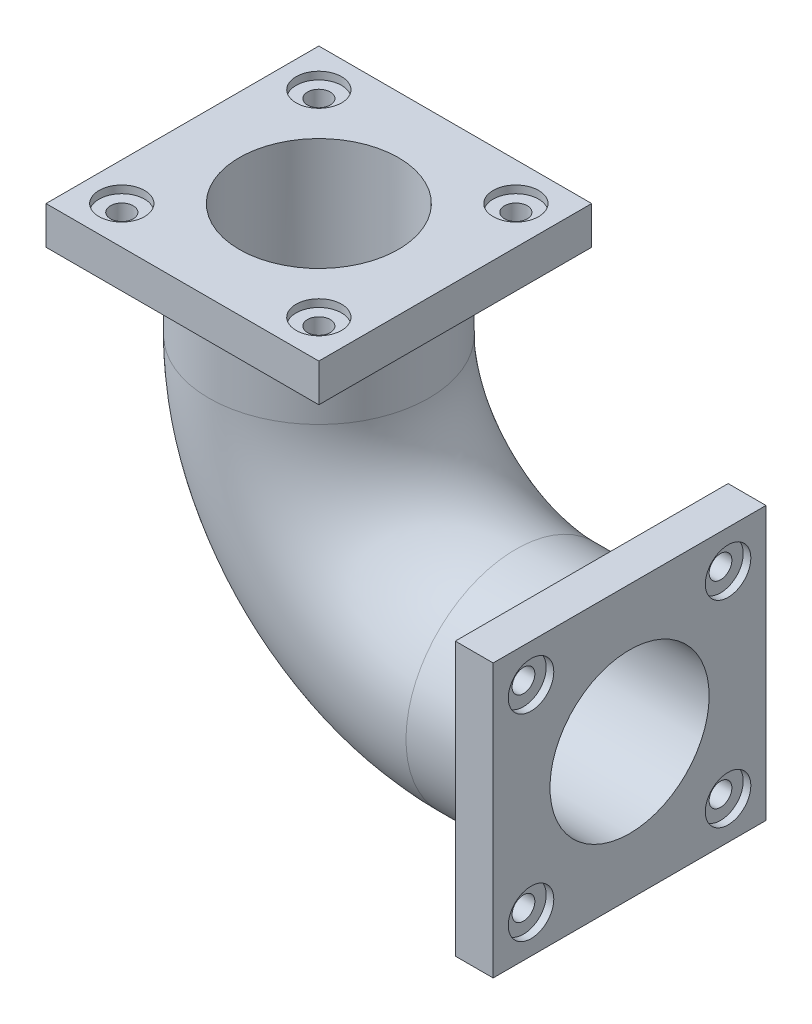
SolidWorks part; units mm, degrees
ref_plane "Ön Düzlem" through (0, 0, 0) normal (0, 0, 1) x (1, 0, 0)
ref_plane "Üst Düzlem" through (0, 0, 0) normal (0, 1, 0) x (1, 0, 0)
ref_plane "Sağ Düzlem" through (0, 0, 0) normal (1, 0, 0) x (0, 0, -1)
sketch "Çizim1" plane through (0, 0, 0) normal (0, 0, 1) x (1, 0, 0)
  line L0 (0, 0) -> (-150, 0)
  line L1 (-410, 260) -> (-410, 410)
  arc A0 (-150, 0) -> (-410, 260) centre (-150, 260) cw
  dimension "D3" = 260
  dimension "D1" = 150
  dimension "D2" = 150
  dimension "D4" = 410
sketch "Çizim4" plane through (0, 0, 0) normal (1, 0, 0) x (0, 0, -1)
  circle A0 centre (0, 0) radius 145
  dimension "D1" = 290
sweep "Süpür1" add profiles "Çizim4" path "Çizim1"
sketch "Çizim5" plane through (0, 410, 0) normal (0, 1, 0) x (1, 0, 0)
  line L0 (-410, 145) -> (-410, -145) construction
  line L3 (-590, 180) -> (-230, 180)
  line L4 (-590, 180) -> (-590, -180)
  line L5 (-590, -180) -> (-230, -180)
  line L6 (-230, 180) -> (-230, -180)
  line L7 (-590, 180) -> (-230, -180) construction
  line L8 (-590, -180) -> (-230, 180) construction
  point P2 (-410, 0)
  point P12 (-410, 0)
  dimension "D2" = 360
  dimension "D1" = 360
extrude "Yükseklik-Ekstrüzyon1" add sketch "Çizim5" against normal blind 50
sketch "Çizim6" plane through (0, 0, 0) normal (1, 0, 0) x (0, 0, -1)
  line L1 (-180, 180) -> (180, 180)
  line L2 (-180, 180) -> (-180, -180)
  line L3 (-180, -180) -> (180, -180)
  line L4 (180, 180) -> (180, -180)
  line L5 (-180, 180) -> (180, -180) construction
  line L6 (-180, -180) -> (180, 180) construction
  point P0 (0, 0)
  dimension "D1" = 360
  dimension "D2" = 360
extrude "Yükseklik-Ekstrüzyon2" add sketch "Çizim6" against normal blind 50
sketch "Çizim7" plane through (0, 410, 0) normal (0, 1, 0) x (1, 0, 0)
  line L0 (-230, 180) -> (-590, 180) construction
  line L1 (-590, 180) -> (-590, -180) construction
  line L2 (-590, -180) -> (-230, -180) construction
  line L3 (-230, -180) -> (-230, 180) construction
  circle A0 centre (-540, 130) radius 15
  circle A1 centre (-280, 130) radius 15
  circle A2 centre (-540, -130) radius 15
  circle A3 centre (-280, -130) radius 15
  point P12 (-802.0645, 261.2808)
  point P17 (0, 0)
  dimension "D3" = 30
  dimension "D5" = 30
  dimension "D7" = 30
  dimension "D1" = 50
  dimension "D2" = 50
  dimension "D4" = 50
  dimension "D6" = 50
extrude "Kes-Ekstrüzyon1" cut sketch "Çizim7" against normal blind 50
sketch "Çizim8" plane through (0, 410, 0) normal (0, 1, 0) x (1, 0, 0)
  circle A0 centre (-540, 130) radius 30
  circle A1 centre (-280, 130) radius 30
  circle A2 centre (-280, -130) radius 30
  circle A3 centre (-540, -130) radius 30
  dimension "D1" = 60
  dimension "D2" = 60
  dimension "D3" = 60
  dimension "D4" = 60
extrude "Kes-Ekstrüzyon2" cut sketch "Çizim8" against normal blind 10
sketch "Çizim9" plane through (0, 0, 0) normal (1, 0, 0) x (0, 0, -1)
  line L0 (-180, 180) -> (-180, -180) construction
  line L1 (180, 180) -> (-180, 180) construction
  line L2 (-180, -180) -> (180, -180) construction
  line L3 (180, -180) -> (180, 180) construction
  circle A0 centre (-130, 130) radius 15
  circle A1 centre (130, 130) radius 15
  circle A2 centre (130, -130) radius 15
  circle A3 centre (-130, -130) radius 15
  point P8 (114.6915, 128.9846)
  point P9 (-88.9783, 129.5306)
  point P10 (117.4216, -114.5455)
  dimension "D3" = 30
  dimension "D1" = 50
  dimension "D2" = 50
  dimension "D4" = 50
  dimension "D5" = 50
extrude "Yükseklik-Ekstrüzyon3" add sketch "Çizim9" against normal blind 50
extrude "Kes-Ekstrüzyon3" cut sketch "Çizim9<2>" against normal blind 50
sketch "Çizim9<2>" plane through (0, 0, 0) normal (1, 0, 0) x (0, 0, -1) same geometry as "Çizim9"
sketch "Çizim10" plane through (0, 0, 0) normal (1, 0, 0) x (0, 0, -1)
  circle A0 centre (-130, 130) radius 30
  circle A1 centre (130, 130) radius 30
  circle A2 centre (130, -130) radius 30
  circle A3 centre (-130, -130) radius 30
  dimension "D1" = 60
  dimension "D2" = 60
  dimension "D3" = 60
  dimension "D4" = 60
extrude "Kes-Ekstrüzyon4" cut sketch "Çizim10" against normal blind 10
sketch "Çizim11" plane through (0, 0, 0) normal (0, 0, 1) x (1, 0, 0)
  line L0 (-50, 0) -> (-150, 0)
  line L1 (-50, 180) -> (-50, -180) construction
  line L2 (-150, 145) -> (-150, -145) construction
  line L3 (-265, 260) -> (-555, 260) construction
  line L4 (-410, 260) -> (-410, 360)
  line L5 (-555, 360) -> (-265, 360) construction
  arc A0 (-150, 0) -> (-410, 260) centre (-150, 260) cw
sketch "Çizim12" plane through (0, 0, 0) normal (1, 0, 0) x (0, 0, -1)
  circle A0 centre (0, 0) radius 105
  dimension "D1" = 210
sweep "Kes-Süpür2" cut path "Çizim11" circular profile diameter 210 parameters "D3"=210
sketch "Çizim47" plane through (0, 0, 0) normal (1, 0, 0) x (0, 0, -1)
  circle A0 centre (0, 0) radius 105
  dimension "D1" = 210
extrude "Kes-Ekstrüzyon5" cut sketch "Çizim47" against normal blind 50
sketch "Çizim48" plane through (0, 410, 0) normal (0, 1, 0) x (1, 0, 0)
  line L2 (-230, 180) -> (-590, 180) construction
  line L4 (-230, -180) -> (-230, 180) construction
  circle A0 centre (-410, 0) radius 105
  point P2 (0, 0)
  dimension "D1" = 210
  dimension "D2" = 180
  dimension "D3" = 180
extrude "Kes-Ekstrüzyon6" cut sketch "Çizim48" against normal blind 50
